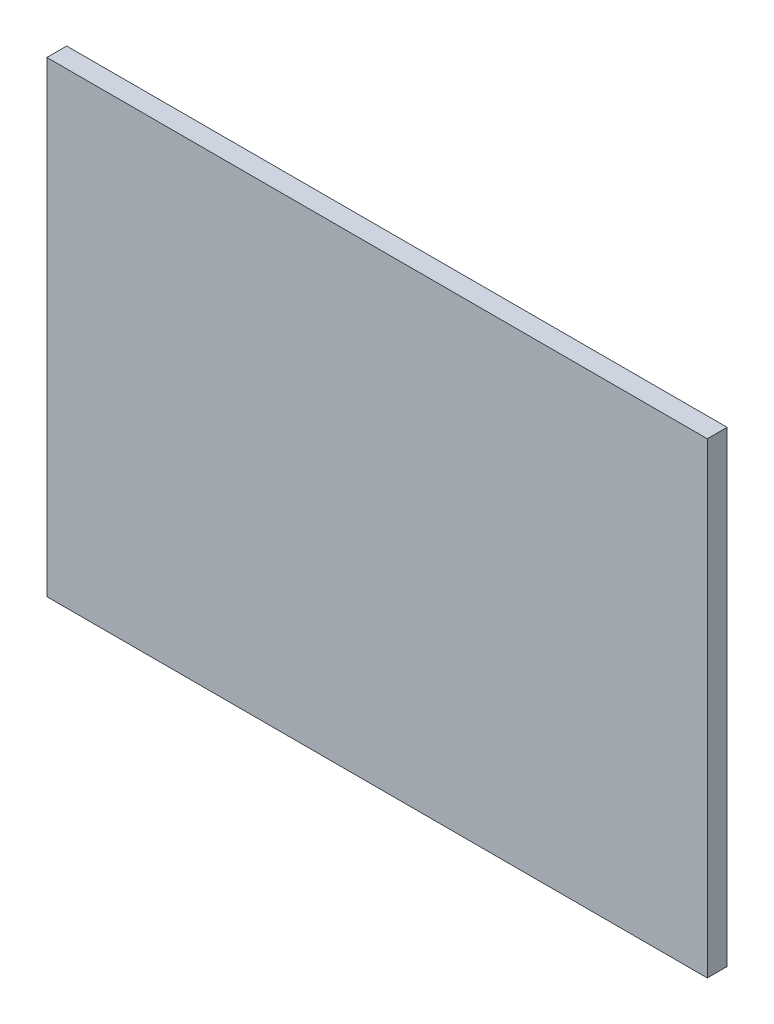
SolidWorks part; units mm, degrees
ref_plane "Front Plane" through (0, 0, 0) normal (0, 0, 1) x (1, 0, 0)
ref_plane "Top Plane" through (0, 0, 0) normal (0, 1, 0) x (1, 0, 0)
ref_plane "Right Plane" through (0, 0, 0) normal (1, 0, 0) x (0, 0, -1)
sketch "Sketch1" plane through (0, 0, 0) normal (0, 0, 1) x (1, 0, 0)
  line L1 (15, 110.7071) -> (115, 110.7071)
  line L2 (15, 110.7071) -> (15, 40)
  line L3 (15, 40) -> (115, 40)
  line L4 (115, 110.7071) -> (115, 40)
  point P4 (156.5798, 128.5696)
  point P5 (25.8572, 38.3804)
  dimension "D1" = 70.7071
  dimension "D2" = 100
extrude "Boss-Extrude1" add sketch "Sketch1" along normal blind 3
